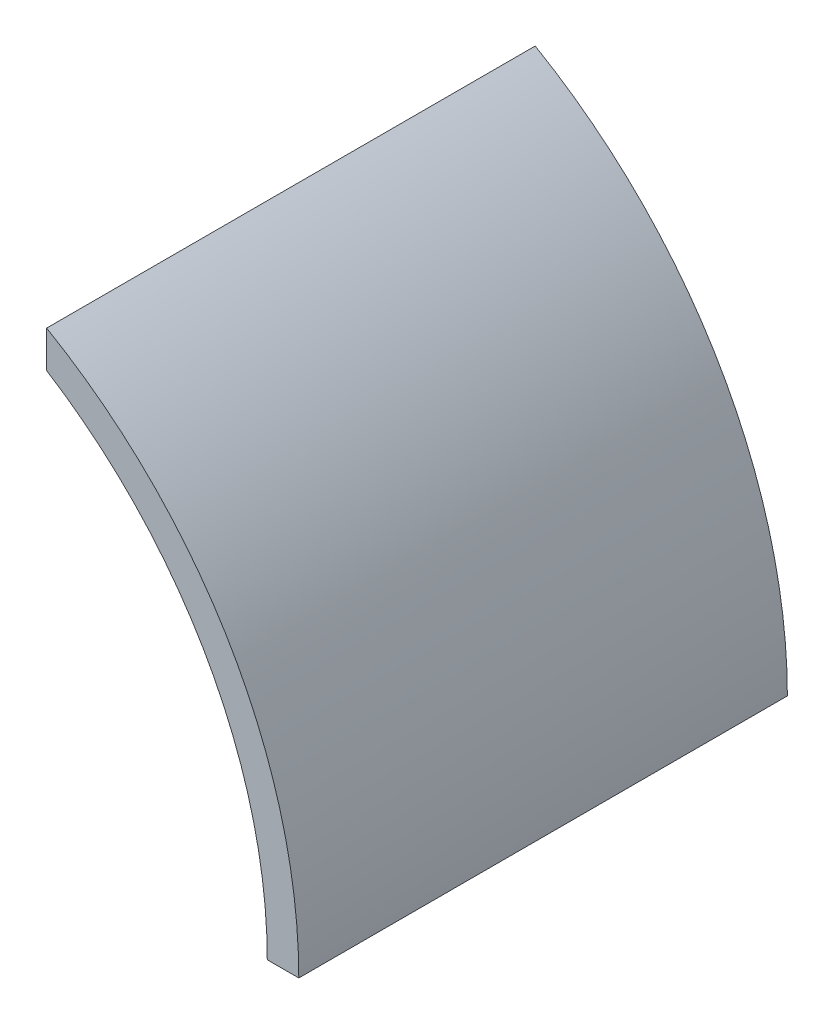
SolidWorks part; units mm, degrees
material "201 Annealed Stainless Steel (SS)"
ref_plane "Front Plane" through (0, 0, 0) normal (0, 0, 1) x (1, 0, 0)
ref_plane "Top Plane" through (0, 0, 0) normal (0, 1, 0) x (1, 0, 0)
ref_plane "Right Plane" through (0, 0, 0) normal (1, 0, 0) x (0, 0, -1)
sketch "Sketch2" plane through (0, 0, 0) normal (0, 0, 1) x (1, 0, 0)
  line L0 (-150, 0) -> (150, 0) construction
  line L1 (0, 150) -> (0, -160) construction
  line L2 (80, 0) -> (80, 108.9269) construction
  line L7 (80, 138.5641) -> (80, 126.8858)
  line L8 (0, -160) -> (0, -160.382) construction
  line L21 (150, 0) -> (160, 0)
  circle A0 centre (0, 0) radius 150 construction
  circle A1 centre (0, 0) radius 160 construction
  arc A2 (80, 126.8858) -> (150, 0) centre (0, 0) cw
  arc A3 (160, 0) -> (80, 138.5641) centre (0, 0) ccw
  dimension "D1" = 300
  dimension "D2" = 320
  dimension "D3" = 80
extrude "Inner Ring - Right Side" add sketch "Sketch2" along normal blind 155
